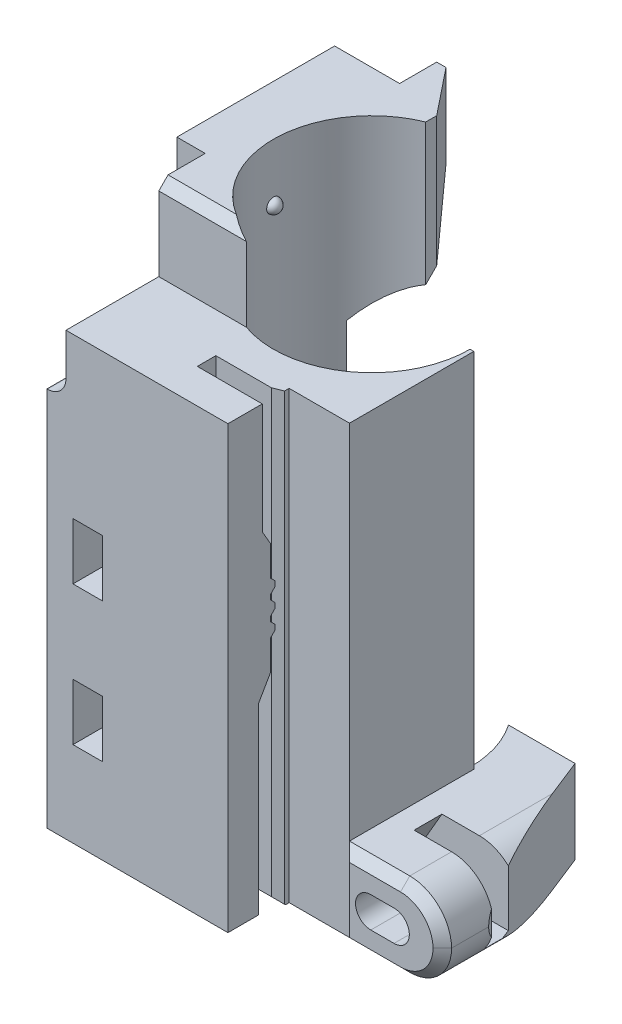
SolidWorks part; units mm, degrees
material "Custom Plastic"
ref_plane "Front Plane" through (0, 0, 0) normal (0, 0, 1) x (1, 0, 0)
ref_plane "Top Plane" through (0, 0, 0) normal (0, 1, 0) x (1, 0, 0)
ref_plane "Right Plane" through (0, 0, 0) normal (1, 0, 0) x (0, 0, -1)
sketch "Sketch2" plane through (0, 0, 0) normal (0, 1, 0) x (1, 0, 0)
  line L0 (22, -14.4) -> (22, -9.4)
  line L1 (16, 6) -> (16, -12.9) construction
  line L2 (11, -13.4) -> (4.5, -13.4)
  line L3 (4.5, -13.4) -> (4.5, -20)
  line L4 (4.5, -20) -> (-15, -20)
  line L5 (-15, -20) -> (-15, 16)
  line L6 (22, -9.4) -> (14.1647, -9.4) construction
  line L7 (8.7384, 6) -> (15.906, 6)
  line L8 (-15, 16) -> (-4, 16)
  line L9 (-4, 16) -> (-4, 9.8163)
  line L10 (11, -13.4) -> (12, -14.4)
  line L11 (12, -14.4) -> (22, -14.4)
  line L12 (22, -9.4) -> (15.906, 6)
  circle A0 centre (0, 0) radius 10.5 construction
  arc A1 (-4, 9.8163) -> (8.7384, 6) centre (0, 0) ccw
  arc A3 (14.1647, -9.4) -> (15.906, 6) centre (0, 0) ccw construction
  dimension "D1" = 21
  dimension "D2" = 0.1
  dimension "D11" = 17
  dimension "D3" = 4.5
  dimension "D4" = 16
  dimension "D5" = 15
  dimension "D6" = 13.4
  dimension "D7" = 20
  dimension "D8" = 16
  dimension "D9" = 4
  dimension "D10" = 6
  dimension "D12" = 22
  dimension "D14" = 45
  dimension "D15" = 11
  dimension "D16" = 1
extrude "Boss-Extrude1" add sketch "Sketch2" along normal blind 37 and the other way blind 20
sketch "Sketch3" plane through (0, 0, 0) normal (0, -1, 0) x (1, 0, 0)
  circle A0 centre (0, 0) radius 10.5
  dimension "D1" = 21
extrude "Cut-Extrude1" [suppressed] cut sketch "Sketch3" against normal blind 20 from offset 4 offset against normal yes
mirror "Mirror1" [suppressed] about plane through (0, 0, 0) normal (0, 1, 0)
sketch "Sketch4" plane through (0, 37, 0) normal (0, -1, 0) x (1, 0, 0)
  line L0 (4.5, 20) -> (4.5, 13.4) construction
  line L1 (-15, 20) -> (4.5, 20)
  line L2 (-15, 20) -> (-15, 9.9962)
  line L3 (-15, 9.9962) -> (4.5, 9.9962)
  line L4 (4.5, 20) -> (4.5, 9.9962)
extrude "Cut-Extrude3" [suppressed] cut sketch "Sketch4" along normal blind 11
sketch "Sketch5" plane through (4.5, 0, 0) normal (1, 0, 0) x (0, 0, -1)
  line L0 (-15.4, 5.718) -> (-14.9, 6.218)
  line L1 (-14.3, -20) -> (-16.3, -20)
  line L2 (-14.3, -20) -> (-14.3, 37)
  line L3 (-16.3, 37) -> (-14.3, 37)
  line L4 (-15.4, 2.5) -> (-15.4, 5.718)
  line L5 (-14.9, 6.218) -> (-14.9, 6.718)
  line L6 (-14.9, 6.718) -> (-15.4, 7.218)
  line L7 (-15.4, 9.782) -> (-14.9, 10.282)
  line L8 (-14.9, 10.282) -> (-14.9, 10.782)
  line L9 (-14.9, 10.782) -> (-15.4, 11.282)
  line L10 (-15.4, 7.75) -> (-14.9, 8.25)
  line L11 (-14.9, 8.25) -> (-14.9, 8.75)
  line L12 (-14.9, 8.75) -> (-15.4, 9.25)
  line L13 (-15.4, 9.25) -> (-15.4, 9.782)
  line L14 (-15.4, 2.5) -> (-16.3, 0.9412)
  line L15 (-15.4, 7.218) -> (-15.4, 7.75)
  line L16 (-16.3, 0.9412) -> (-16.3, -20)
  line L17 (-15.4, 11.282) -> (-15.4, 14.5)
  line L18 (-15.4, 14.5) -> (-16.3, 16.0588)
  line L19 (-20, -20) -> (-13.4, -20) construction
  line L20 (16, 8.5) -> (-14.9, 8.5) construction
  line L21 (-16.3, 16.0588) -> (-16.3, 37)
  line L22 (-20, 37) -> (-13.4, 37) construction
  line L23 (16, -20) -> (16, 37) construction
  dimension "D1" = 0.5
  dimension "D2" = 0.5
  dimension "D3" = 2.032
  dimension "D4" = 1.1
  dimension "D5" = 2
  dimension "D6" = 14.3
  dimension "D7" = 6
  dimension "D8" = 150
extrude "Cut-Extrude5" cut sketch "Sketch5" against normal blind 7
chamfer "Chamfer1" [suppressed] distance 1.2 angle 45
chamfer "Chamfer3" distance 0.5 angle 45 9 edges at (1, -20, 14.3) (-3.0421, -20, 10.1541) (-4, -20, -12.9082) (-9.5, -20, -16) (-15, -20, 2) (-5.25, -20, 20) (4.5, -20, 18.15) (1, -20, 16.3) (-2.5, -20, 15.3)
sketch "Sketch6" plane through (-15, 0, 0) normal (-1, 0, 0) x (0, 0, 1)
  line L0 (13, 7.5) -> (13, -7.5) construction
  line L1 (0, 0) -> (13, 0) construction
  circle A0 centre (13, 7.5) radius 1.65
  circle A1 centre (13, -7.5) radius 1.65
  dimension "D2" = 3.3
  dimension "D1" = 15
  dimension "D3" = 13
extrude "Cut-Extrude6" cut sketch "Sketch6" against normal blind 10
sketch "Sketch7" plane through (-15, 0, 0) normal (-1, 0, 0) x (0, 0, 1)
  line L0 (21.3141, -4.2) -> (21.3141, -10.3)
  line L1 (9.3668, -7.5) -> (10.9834, -10.3)
  line L2 (10.9834, -10.3) -> (21.3141, -10.3)
  line L3 (11.3834, 4.7) -> (9.7668, 7.5)
  line L4 (21.3141, 4.7) -> (11.3834, 4.7)
  line L5 (21.3141, -4.7) -> (11.3834, -4.7) construction
  line L6 (11.2721, -4.2) -> (9.3668, -7.5)
  line L7 (-3, 8.5) -> (19.4531, 8.5) construction
  line L8 (11.2721, -4.2) -> (21.3141, -4.2)
  line L9 (11.3834, 10.3) -> (21.7141, 10.3) construction
  line L10 (13.1374, -12.1691) -> (15.0359, -8.8809) construction
  line L11 (16.6078, -8.8418) -> (15.5516, -7.0123) construction
  line L12 (9.7668, 7.5) -> (11.6721, 10.8)
  line L13 (21.3141, 4.7) -> (21.3141, 10.8)
  line L14 (11.6721, 10.8) -> (21.3141, 10.8)
  circle A0 centre (12.6, -7.5) radius 2.8 construction
  circle A2 centre (13, 7.5) radius 2.8 construction
  circle A3 centre (13, 7.5) radius 1.65 construction
  point P4 (13, -7.5)
  dimension "D1" = 5.6
  dimension "D2" = 0.4
  dimension "D3" = 0.5
  dimension "D4" = 0.5
extrude "Cut-Extrude7" cut sketch "Sketch7" against normal blind 3.2 from offset 2.8 offset against normal yes
sketch "Sketch9" plane through (-15, 0, 0) normal (-1, 0, 0) x (0, 0, 1)
  line L0 (-16, 28) -> (-6, 18)
  line L1 (-16, -19.5) -> (-16, 37) construction
  line L2 (-6, 18) -> (-6, -20)
  line L3 (-16, -20) -> (20, -20) construction
  line L4 (-6, -20) -> (-16, -20)
  line L5 (-16, -20) -> (-16, 28)
  line L6 (-16, 37) -> (20, 37) construction
  dimension "D1" = 9
  dimension "D2" = 6
  dimension "D3" = 45
extrude "Cut-Extrude9" cut sketch "Sketch9" against normal blind 12 and the other way blind 10
sketch "Sketch12" plane through (-15, 0, 0) normal (-1, 0, 0) x (0, 0, 1)
  line L0 (8, 37) -> (8, 30)
  line L1 (-16, 37) -> (20, 37) construction
  line L2 (5, 25) -> (-13, 25)
  line L3 (-16, 28) -> (-13, 25)
  line L4 (-16, 28) -> (-6, 18) construction
  line L5 (-16, 28) -> (-16, 37)
  line L6 (-16, 37) -> (8, 37)
  line L7 (8, 30) -> (5, 30)
  line L8 (5, 30) -> (5, 25)
  dimension "D1" = 24
  dimension "D2" = 12
  dimension "D3" = 3
  dimension "D4" = 5
extrude "Boss-Extrude2" add sketch "Sketch12" along normal blind 1
sketch "Sketch10" plane through (0, 0, -16) normal (0, 0, -1) x (-1, 0, 0)
  line L1 (16, 37) -> (9, 37)
  line L2 (16, 37) -> (16, 28.8)
  line L3 (16, 28.8) -> (9, 28.8)
  line L4 (9, 37) -> (9, 28.8)
  line L5 (16, 37) -> (16, 28) construction
  line L6 (4, 28) -> (16, 28) construction
  line L7 (4, 37) -> (16, 37) construction
  dimension "D1" = 7
  dimension "D3" = 0.8
extrude "Cut-Extrude10" cut sketch "Sketch10" against normal blind 4
sketch "Sketch11" plane through (-16, 0, 0) normal (-1, 0, 0) x (0, 0, 1)
  line L0 (-12, 28.8) -> (-16, 28.8) construction
  line L2 (-16, 28) -> (-16, 28.8) construction
  circle A0 centre (-9, 26.3) radius 1.25
  circle A1 centre (1, 26.3) radius 1.25
  dimension "D3" = 10
  dimension "D4" = 2.5
  dimension "D1" = 2.5
  dimension "D2" = 7
extrude "Cut-Extrude11" cut sketch "Sketch11" against normal blind 4
chamfer "Chamfer4" distance 3 angle 45 2 edges
sketch "Sketch13" plane through (0, 37, 0) normal (0, 1, 0) x (1, 0, 0)
  line L0 (-16, -10) -> (0, -10)
  line L1 (0, -10) -> (0, 6.4112)
  line L2 (-16, -10) -> (-16, -20)
  line L3 (12, -20) -> (-16, -20)
  line L4 (0, 6.4112) -> (12, 6.4112)
  line L5 (12, -20) -> (12, 6.4112)
  line L7 (-15, -20) -> (4.5, -20) construction
extrude "Cut-Extrude12" cut sketch "Sketch13" against normal blind 9
chamfer "Chamfer5" distance 1 angle 45 1 edges at (-9.7578, 37, 10)
sketch "Sketch15" plane through (0, -20, -7.1) normal (0, 1, 0) x (1, 0, 0)
  line L1 (22, -21.5) -> (11, -21.5)
  line L2 (22, -21.5) -> (22, -1.1)
  line L3 (22, -1.1) -> (8.1933, -1.1)
  line L4 (11, -21.5) -> (11, -7.1)
  line L5 (11, -7.1) -> (8.1933, -7.1)
  line L6 (8.1933, -7.1) -> (8.1933, -1.1)
  dimension "D1" = 11
extrude "Cut-Extrude14" cut sketch "Sketch15" along normal through all from offset 9
chamfer "Chamfer6" distance 1 angle 45 1 edges at (-15, -0.75, -6)
chamfer "Chamfer7" distance 0.4 distance2 1 1 edges at (4.5, 4.25, 14.3) first distance on face at (4.5, -0.7, 13.84)
chamfer "Chamfer10" distance 0.4 distance2 2 1 edges at (4.5, -9.2794, 16.3) first distance on face at (4.5, 7.65, 15.89)
sketch "Sketch17" plane through (0, 0, 14.4) normal (0, 0, 1) x (1, 0, 0)
  line L0 (15.55, -15.5) -> (22, -15.5) construction
  line L1 (22, -20) -> (22, -11) construction
  line L2 (14.3, -15.5) -> (16.8, -15.5) construction
  line L3 (14.3, -13.85) -> (16.8, -13.85)
  line L4 (14.3, -17.15) -> (16.8, -17.15)
  circle A0 centre (15.55, -15.5) radius 4.5 construction
  arc A1 (14.3, -13.85) -> (14.3, -17.15) centre (14.3, -15.5) ccw
  arc A2 (16.8, -17.15) -> (16.8, -13.85) centre (16.8, -15.5) ccw
  point P2 (11.05, -15.5)
  point P9 (15.55, -15.5)
  dimension "D2" = 9
  dimension "D3" = 1.65
  dimension "D1" = 11.05
  dimension "D4" = 2.5
extrude "Cut-Extrude16" cut sketch "Sketch17" against normal blind 6
fillet "Fillet2" radius 4.5 2 edges at (22, -11, 11.9) (22, -20, 11.9)
sketch "Sketch18" plane through (0, 0, 14.4) normal (0, 0, -1) x (-1, 0, 0)
  line L0 (-22.7084, -8.1113) -> (-22.7084, -18.3)
  line L1 (-10.8668, -15.5) -> (-15.1327, -8.1113)
  line L3 (-22.7084, -8.1113) -> (-15.1327, -8.1113)
  line L5 (-22.7084, -18.3) -> (-12.4834, -18.3)
  line L6 (-12.4834, -18.3) -> (-10.8668, -15.5)
  line L9 (-16.4286, -13.9332) -> (-17.2368, -15.3332) construction
  line L10 (-17.3332, -15.5) -> (-15.3536, -18.9286) construction
  line L11 (-12.4834, -12.7) -> (-14.1, -12.7) [skipped]
  circle A0 centre (-14.1, -15.5) radius 2.8 construction
  arc A3 (-14.3, -17.15) -> (-14.3, -13.85) centre (-14.3, -15.5) ccw construction
  point P10 (-14.3, -15.5)
  dimension "D2" = 5.6
  dimension "D1" = 0.2
extrude "Cut-Extrude17" cut sketch "Sketch18" against normal blind 0.5 and the other way blind 2.5 from offset 6
chamfer "Chamfer14" distance 1 angle 45 4 edges at (14.75, -11, 14.4) (20.682, -12.318, 14.4) (20.682, -18.682, 14.4) (14.75, -20, 14.4)
sketch "Sketch19" plane through (0, 0, 20) normal (0, 0, 1) x (1, 0, 0)
  line L0 (-16, 37) -> (-12.95, 37)
  line L1 (-12.95, 37) -> (-12.95, 23.5001)
  line L2 (-14.95, 21.5001) -> (-16, 21.5001)
  line L4 (-16, 37) -> (-5.6, 37) construction
  line L6 (-15, 28) -> (4.5, 28) construction
  line L8 (-16, 37) -> (-16, 21.5001)
  line L10 (-15, -19.5) -> (-15, 28) construction
  line L12 (-16, 33.5678) -> (-13.6361, 31.5078) construction
  line L13 (-16, 30) -> (-16, 36) construction
  arc A0 (-12.95, 30) -> (-13.6361, 31.5078) centre (-14.95, 30) ccw construction
  arc A1 (-14.95, 21.5001) -> (-12.95, 23.5001) centre (-14.95, 23.5001) ccw
  dimension "D1" = 4
  dimension "D2" = 2.05
  dimension "D3" = 2
extrude "Cut-Extrude18" cut sketch "Sketch19" against normal blind 15
chamfer "Chamfer15" distance 4 distance2 5 1 edges at (-4, 32.5, -16) first distance on face at (-9.6667, 31.2667, -16)
sketch "Sketch20" plane through (0, 0, 0) normal (0, 0, 1) x (1, 0, 0)
  line L1 (-10.6, 30.85) -> (-10.6, -13.85) construction
  line L2 (-10.6, 4.25) -> (4.5, 4.25) construction
  line L3 (4.5, -19.5) -> (4.5, 28) construction
  line L4 (-10.6, 30.1) -> (-10.6, 31.6)
  line L5 (-10.6, -13.1) -> (-10.6, -14.6)
  line L6 (4, -20) -> (-14.5, -20) construction
  arc A0 (-10.6, 31.6) -> (-10.6, 30.1) centre (-10.6, 30.85) ccw
  arc A1 (-10.6, -13.1) -> (-10.6, -14.6) centre (-10.6, -13.85) ccw
  dimension "D2" = 1.5
  dimension "D3" = 6.15
  dimension "D1" = 44.7
revolve "Revolve2" add sketch "Sketch20" angle 360 about L1
ref_axis "Axis1" through (0, -19.5, 0) along (0, 1, 0)
equation "\"y-plate-thickness\"=5"
equation "\"bed-plate-thickness\"=6"
equation "\"x-plate-thickness\"=5"
equation "\"rod-diameter\"=12"
equation "\"D1@Sketch15\"=\"rod-diameter\"/2+\"x-plate-thickness\""
equation "\"y-cross-rib-thickness\"=6"
equation "\"y-rib-thickness\"=6"
equation "\"t-nut-hole-diameter\"=3"
equation "\"enclosure-thickness\"=0.6"
equation "\"M3-Clearance\"=3.3"
equation "\"M4-Clearance\"=4.3"
equation "\"M5-Clearance\"=5.3"
equation "\"M6-Clearance\"=6.3"
equation "\"M8-Clearance\"=8.3"
equation "\"623-Bearing-Dia\"=11.2"
